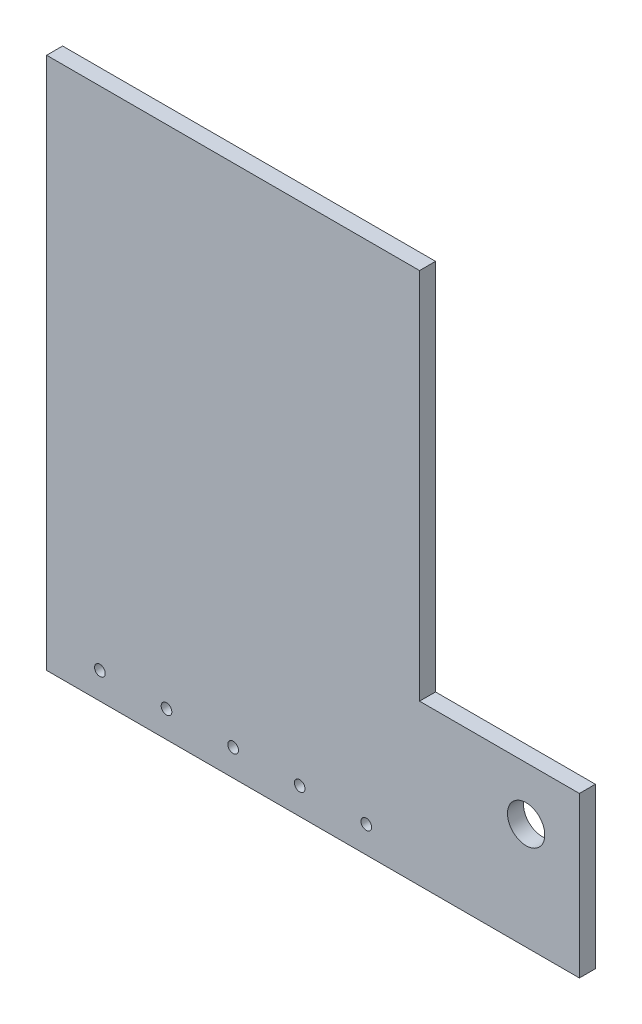
SolidWorks part; units mm, degrees
ref_plane "Plan de face" through (0, 0, 0) normal (0, 0, 1) x (1, 0, 0)
ref_plane "Plan de dessus" through (0, 0, 0) normal (0, 1, 0) x (1, 0, 0)
ref_plane "Plan de droite" through (0, 0, 0) normal (1, 0, 0) x (0, 0, -1)
sketch "Esquisse1" plane through (0, 0, 0) normal (0, 0, 1) x (1, 0, 0)
  line L1 (0, 0) -> (140, 0)
  line L2 (0, 0) -> (0, 200)
  line L3 (0, 200) -> (140, 200)
  line L4 (140, 0) -> (140, 200)
  dimension "D1" = 200
  dimension "D2" = 140
extrude "Boss.-Extru.1" add sketch "Esquisse1" along normal blind 6
sketch "Esquisse2" plane through (0, 0, 6) normal (0, 0, 1) x (1, 0, 0)
  line L0 (70, 0) -> (70, 200) construction
  line L1 (0, 0) -> (140, 0) construction
  line L2 (140, 200) -> (0, 200) construction
  line L3 (120, 10) -> (95, 10) construction
  line L4 (95, 10) -> (70, 10) construction
  line L5 (20, 10) -> (45, 10) construction
  circle A0 centre (95, 10) radius 2
  circle A1 centre (120, 10) radius 2
  circle A2 centre (20, 10) radius 2
  circle A3 centre (45, 10) radius 2
  circle A4 centre (70, 10) radius 2
  dimension "D2" = 4
  dimension "D3" = 25
  dimension "D4" = 25
  dimension "D1" = 10
extrude "Enlèv. mat.-Extru.1" cut sketch "Esquisse2" against normal through all
sketch "Esquisse3" plane through (0, 0, 6) normal (0, 0, 1) x (1, 0, 0)
  line L1 (140, 0) -> (200, 0)
  line L2 (140, 0) -> (140, 60)
  line L3 (140, 60) -> (200, 60)
  line L4 (200, 0) -> (200, 60)
  dimension "D1" = 60
  dimension "D2" = 60
extrude "Boss.-Extru.2" add sketch "Esquisse3" against normal up to vertex (6 mm away) up to point (140, 200, 0)
sketch "Esquisse4" plane through (0, 0, 6) normal (0, 0, 1) x (1, 0, 0)
  line L0 (180, 0) -> (180, 60) construction
  line L1 (0, 0) -> (200, 0) construction
  line L2 (200, 60) -> (140, 60) construction
  circle A0 centre (180, 40) radius 7
  circle A1 centre (70, 10) radius 2 construction
  dimension "D1" = 14
  dimension "D2" = 40
  dimension "D3" = 110
extrude "Enlèv. mat.-Extru.2" cut sketch "Esquisse4" against normal up to vertex (6 mm away) up to point (140, 200, 0)
